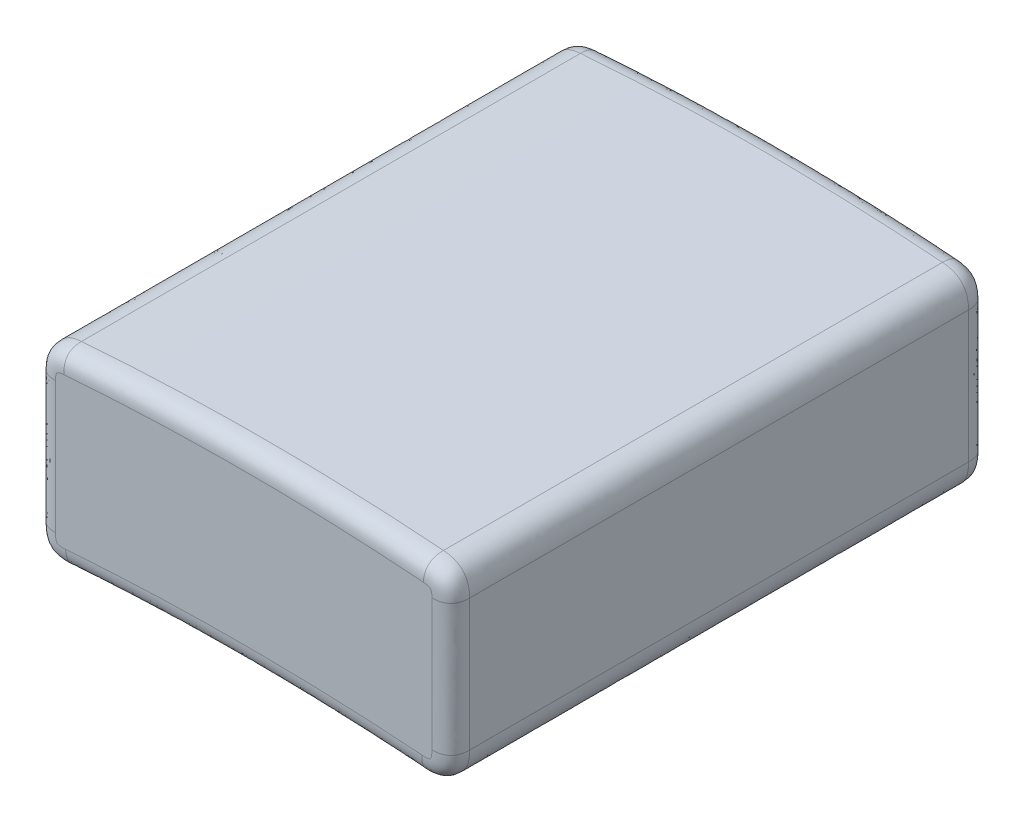
SolidWorks part; units mm, degrees
ref_plane "Alzado" through (0, 0, 0) normal (0, 0, 1) x (1, 0, 0)
ref_plane "Planta" through (0, 0, 0) normal (0, 1, 0) x (1, 0, 0)
ref_plane "Vista lateral" through (0, 0, 0) normal (1, 0, 0) x (0, 0, -1)
sketch "Croquis3" plane through (0, 0, 0) normal (0, 0, 1) x (1, 0, 0)
  line L0 (0, 0) -> (0, 20)
  line L1 (44, 0) -> (44, 20)
  arc A0 (0, 0) -> (44, 0) centre (22, -253.7838) cw
  arc A1 (0, 20) -> (44, 20) centre (22, -233.7838) cw
  point P3 (44, 20.6777)
  point P9 (0, 20.6777)
extrude "Saliente-Extruir2" add sketch "Croquis3" along normal blind 57
sketch "Croquis4" plane through (0, 0, 0) normal (0, 0, 1) x (1, 0, 0)
  line L0 (2, 2) -> (2, 18)
  line L1 (42, 2) -> (42, 18)
  arc A0 (2, 2) -> (42, 2) centre (22, -251.9492) cw
  arc A1 (2, 18) -> (42, 18) centre (22, -235.9492) cw
  point P6 (0, 0)
  point P7 (0, 0)
  point P8 (0, 0)
  point P9 (0, 0)
  point P10 (0, 0)
  point P11 (0, 0)
  point P12 (0, 0)
extrude "Cortar-Extruir3" cut sketch "Croquis4" along normal blind 55
fillet "Redondeo3" radius 3 4 edges at (44, 0, 28.5) (44, 20, 28.5) (0, 20, 28.5) (0, 0, 28.5)
fillet "Redondeo7" radius 2 15 edges
